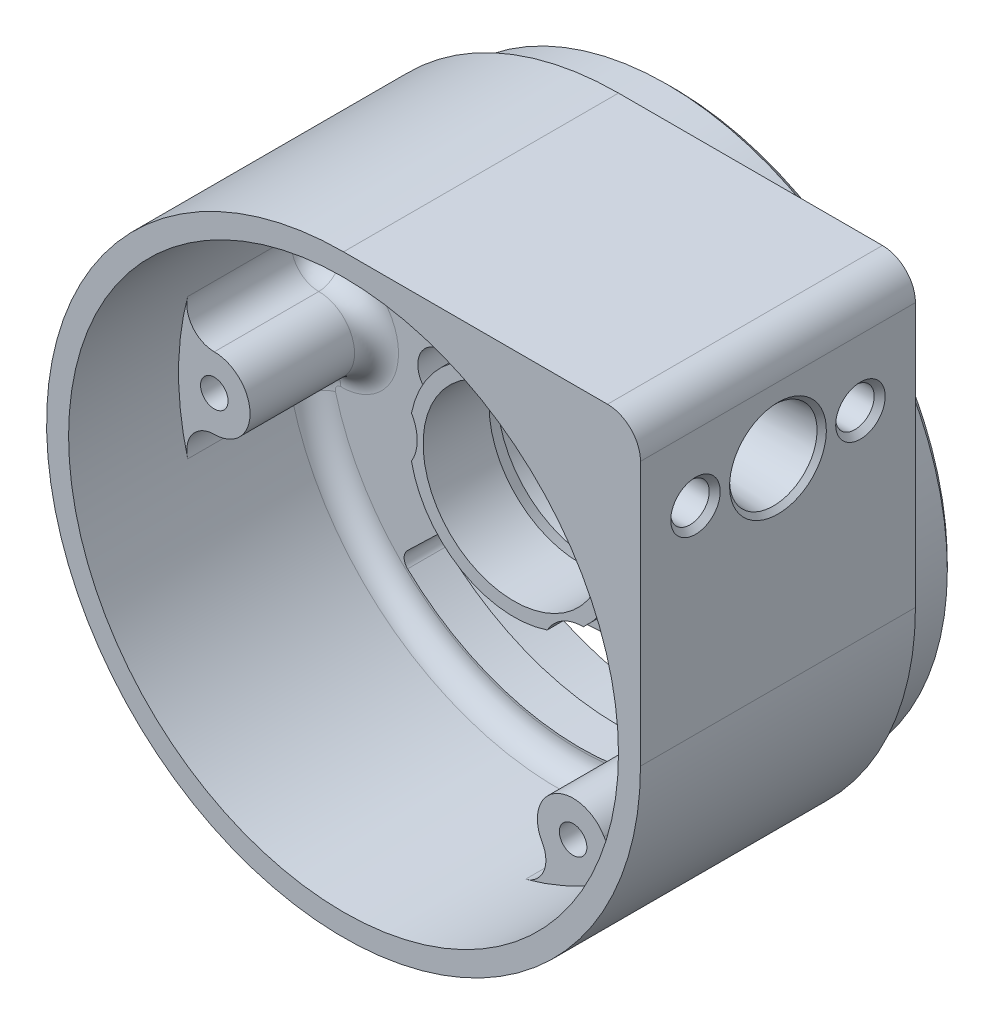
SolidWorks part; units mm, degrees
ref_plane "Front Plane" through (0, 0, 0) normal (0, 0, 1) x (1, 0, 0)
ref_plane "Top Plane" through (0, 0, 0) normal (0, 1, 0) x (1, 0, 0)
ref_plane "Right Plane" through (0, 0, 0) normal (1, 0, 0) x (0, 0, -1)
sketch "Sketch1" plane through (0, 0, 0) normal (0, 0, 1) x (1, 0, 0)
  line L0 (-12.5, 0) -> (0, 0) construction
  line L1 (0, 0) -> (6.25, 10.8253) construction
  line L2 (6.25, -10.8253) -> (0, 0) construction
  circle A0 centre (0, 0) radius 27
  circle A1 centre (0, 0) radius 12.5 construction
  circle A2 centre (0, 0) radius 7.75
  circle A3 centre (0, 0) radius 3 construction
  circle A4 centre (6.25, 10.8253) radius 2.25
  circle A5 centre (-12.5, 0) radius 2.25
  circle A6 centre (6.25, -10.8253) radius 2.25
  dimension "D1" = 54
  dimension "D2" = 6
  dimension "D3" = 15.5
  dimension "D4" = 25
  dimension "D7" = 4.5
  dimension "D5" = 120
  dimension "D6" = 120
extrude "Boss-Extrude1" add sketch "Sketch1" along normal blind 21
sketch "Sketch2" plane through (0, 0, 21) normal (0, 0, 1) x (1, 0, 0)
  circle A0 centre (6.25, 10.8253) radius 3.75
  circle A1 centre (6.25, -10.8253) radius 3.75
  circle A2 centre (-12.5, 0) radius 3.75
  dimension "D1" = 7.5
extrude "Cut-Extrude1" cut sketch "Sketch2" against normal offset from surface (16.5 mm away) 4.5 up to face at (27, 0, 0)
sketch "Sketch3" plane through (0, 0, 21) normal (0, 0, 1) x (1, 0, 0)
  line L0 (13.9654, 0) -> (0, 13.9654) construction
  line L1 (0, -17.6777) -> (17.6777, 0) construction
  line L2 (0, -17.6777) -> (-17.6777, 0) construction
  line L3 (-17.6777, 0) -> (0, 17.6777) construction
  line L4 (17.6777, 0) -> (0, 17.6777) construction
  line L5 (0, -17.6777) -> (0, 17.6777) construction
  line L6 (-17.6777, 0) -> (17.6777, 0) construction
  line L7 (0, 13.9654) -> (-13.9654, 0) construction
  line L8 (-13.9654, 0) -> (0, -13.9654) construction
  line L9 (0, -13.9654) -> (13.9654, 0) construction
  line L10 (-17.9605, 0) -> (0, 17.9605)
  line L11 (17.9605, 0) -> (0, 17.9605)
  line L12 (0, -17.9605) -> (17.9605, 0)
  line L13 (0, -17.9605) -> (-17.9605, 0)
  circle A0 centre (13.9654, 0) radius 1.625 construction
  circle A1 centre (0, -13.9654) radius 1.625 construction
  circle A2 centre (-13.9654, 0) radius 1.625 construction
  circle A3 centre (0, 13.9654) radius 1.625 construction
  point P0 (0, 0)
  dimension "D2" = 3.25
  dimension "D3" = 1
  dimension "D1" = 25
  dimension "D4" = 0.2
sketch "Sketch5" plane through (0, 0, 21) normal (0, 0, 1) x (1, 0, 0)
  line L0 (0, 27) -> (24, 27)
  line L3 (27, 0) -> (27, 24)
  circle A0 centre (0, 0) radius 27 construction
  arc A1 (0, 27) -> (27, 0) centre (0, 0) cw
  arc A3 (24, 27) -> (27, 24) centre (24, 24) cw
  circle M11 centre (0, 0) radius 27
extrude "Boss-Extrude2" add sketch "Sketch5" against normal up to surface (21 mm away) contours A3 L0 M11 | M11 region at (20.9021, 20.9021, 21) up to face at (27, 0, 0)
sketch "Sketch8" plane through (0, 0, 0) normal (0, 0, -1) x (-1, 0, 0)
  circle A0 centre (0, 0) radius 8.625
  dimension "D1" = 17.25
extrude "Cut-Extrude5" cut sketch "Sketch8" against normal blind 2
chamfer "Chamfer2" distance 1 angle 72 1 edges at (-7.75, 0, 2) first distance on face at (-7.75, 0, 2)
sketch "Sketch9" plane through (0, 0, 21) normal (0, 0, 1) x (1, 0, 0)
  circle A0 centre (0, 0) radius 25
  dimension "D1" = 50
extrude "Cut-Extrude6" cut sketch "Sketch9" against normal offset from surface (17.5 mm away) 3.5 up to face at (-8.625, 0, 0)
sketch "Sketch10" plane through (0, 0, 3.5) normal (0, 0, 1) x (1, 0, 0)
  line L0 (0, 0) -> (11.1505, 11.1233) construction
  line L1 (0, 0) -> (4.0578, -15.2183) construction
  line L2 (0, 0) -> (-15.2083, 4.095) construction
  line L3 (0, 0) -> (-2.716, 15.5141) construction
  line L4 (0, 0) -> (-12.0776, -10.1091) construction
  line L5 (0, 0) -> (13.8224, -5.0501) construction
  line L6 (-14.21, 3.8262) -> (-12.2736, 3.3048)
  line L7 (-2.1919, 12.5203) -> (-2.5377, 14.4956)
  line L8 (10.4185, 10.3931) -> (8.9988, 8.9768)
  line L9 (11.9388, -4.3619) -> (14.7936, -5.4049)
  line L10 (3.7914, -14.2193) -> (3.2748, -12.2816)
  line L11 (-9.747, -8.1584) -> (-11.2847, -9.4455)
  circle A0 centre (0, 0) radius 15.75 construction
  circle A1 centre (0, 0) radius 11.75 construction
  circle A2 centre (6.25, 10.8253) radius 2.25 construction
  arc A3 (-1.6579, 15.6625) -> (10.3708, 11.8537) centre (0, 0) cw
  arc A4 (14.3931, -6.3954) -> (5.0802, -14.9082) centre (0, 0) cw
  arc A5 (-15.451, 3.0545) -> (-12.7351, -9.2671) centre (0, 0) ccw
  arc A6 (-11.0713, 3.9355) -> (-2.9277, 11.3794) centre (0, 0) cw
  arc A7 (8.9439, 7.6203) -> (11.3187, -3.1542) centre (0, 0) cw
  arc A8 (2.1275, -11.5558) -> (-8.391, -8.2252) centre (0, 0) cw
  arc A9 (-8.391, -8.2252) -> (-9.747, -8.1584) centre (-9.1051, -8.9252) ccw
  arc A10 (2.1275, -11.5558) -> (3.2748, -12.2816) centre (2.3085, -12.5393) cw
  arc A11 (3.7914, -14.2193) -> (5.0802, -14.9082) centre (4.7577, -13.9616) ccw
  arc A12 (11.3187, -3.1542) -> (11.9388, -4.3619) centre (12.282, -3.4227) ccw
  arc A13 (14.3931, -6.3954) -> (13.8224, -5.0501) centre (13.4792, -5.9894) ccw
  arc A14 (8.9439, 7.6203) -> (8.9988, 8.9768) centre (9.7051, 8.2689) cw
  arc A15 (10.4185, 10.3931) -> (10.3708, 11.8537) centre (9.7123, 11.1011) ccw
  arc A16 (-2.5377, 14.4956) -> (-1.6579, 15.6625) centre (-1.5527, 14.6681) cw
  arc A17 (-2.9277, 11.3794) -> (-2.1919, 12.5203) centre (-3.1769, 12.3479) ccw
  arc A18 (-11.0713, 3.9355) -> (-12.2736, 3.3048) centre (-12.0136, 4.2704) cw
  arc A19 (-14.21, 3.8262) -> (-15.451, 3.0545) centre (-14.47, 2.8606) ccw
  arc A20 (-12.7351, -9.2671) -> (-11.2847, -9.4455) centre (-11.9266, -8.6787) ccw
  point P23 (-9.0103, -7.5417)
  point P26 (3.0272, -11.3533)
  point P31 (11.0365, -4.0322)
  point P37 (8.3187, 8.2983)
  point P46 (-2.0262, 11.574)
  point P49 (-11.3459, 3.055)
  dimension "D1" = 23.5
  dimension "D2" = 31.5
  dimension "D6" = 55
  dimension "D9" = 1
  dimension "D3" = 120
  dimension "D4" = 120
  dimension "D5" = 1
  dimension "D7" = 55
  dimension "D8" = 55
sketch "Sketch11" plane through (0, 0, 3.5) normal (0, 0, 1) x (1, 0, 0)
  line L0 (-3.3134, 13.3589) -> (-5.2425, 21.1366)
  line L1 (-13.0084, 4.4969) -> (-20.5819, 7.1151)
  line L2 (10.3986, 9.0171) -> (16.4528, 14.2669)
  line L3 (-14.21, 3.8262) -> (-12.2736, 3.3048) construction
  line L4 (-2.1919, 12.5203) -> (-2.5377, 14.4956) construction
  line L5 (13.2259, -3.81) -> (20.9261, -6.0282)
  line L6 (2.6097, -13.514) -> (4.1291, -21.382)
  line L7 (-9.9125, -9.549) -> (-15.6836, -15.1084)
  line L8 (0, 0) -> (-3.9736, 12.1676) construction
  line L9 (0, 0) -> (12.5242, -2.6426) construction
  arc A0 (-3.9736, 12.1676) -> (-11.7627, 5.0477) centre (0, 0) ccw
  circle A1 centre (0, 0) radius 25 construction
  arc A2 (-21.1843, 8.4299) -> (-20.5819, 7.1151) centre (-20.2552, 8.0602) ccw
  arc A3 (-6.4981, 21.8544) -> (-21.1843, 8.4299) centre (0, 0) ccw
  arc A4 (-11.7627, 5.0477) -> (-13.0084, 4.4969) centre (-12.6816, 5.4421) cw
  arc A5 (-3.9736, 12.1676) -> (-3.3134, 13.3589) centre (-4.284, 13.1182) ccw
  arc A6 (-5.2425, 21.1366) -> (-6.4981, 21.8544) centre (-6.2131, 20.8959) ccw
  arc A7 (10.2528, 7.6629) -> (10.3986, 9.0171) centre (11.0538, 8.2616) cw
  arc A8 (17.8927, 14.1312) -> (16.4528, 14.2669) centre (17.1079, 13.5114) ccw
  arc A9 (22.1755, -5.2997) -> (17.8927, 14.1312) centre (0, 0) ccw
  arc A10 (20.9261, -6.0282) -> (22.1755, -5.2997) centre (21.2029, -5.0672) ccw
  arc A11 (12.5242, -2.6426) -> (13.2259, -3.81) centre (13.5027, -2.849) ccw
  arc A12 (12.5242, -2.6426) -> (10.2528, 7.6629) centre (0, 0) ccw
  arc A13 (1.5099, -12.7106) -> (2.6097, -13.514) centre (1.6279, -13.7037) cw
  arc A14 (3.2916, -22.5611) -> (4.1291, -21.382) centre (3.1473, -21.5716) ccw
  arc A15 (-15.6774, -16.5547) -> (3.2916, -22.5611) centre (0, 0) ccw
  arc A16 (-15.6836, -15.1084) -> (-15.6774, -16.5547) centre (-14.9898, -15.8286) ccw
  arc A17 (-8.5507, -9.525) -> (-9.9125, -9.549) centre (-9.2187, -10.2692) ccw
  arc A18 (-8.5507, -9.525) -> (1.5099, -12.7106) centre (0, 0) ccw
  dimension "D3" = 10
  dimension "D4" = 2.2
  dimension "D5" = 1
  dimension "D1" = 4
  dimension "D2" = 4
  dimension "D6" = 120
extrude "Cut-Extrude7" cut sketch "Sketch11" against normal through all
sketch "Sketch13" plane through (0, 0, 0) normal (0, 0, -1) x (-1, 0, 0)
  circle A0 centre (0, 0) radius 24.2
  arc A1 (-27, 0) -> (0, 27) centre (0, 0) ccw construction
  circle A2 centre (0, 0) radius 25.5
  dimension "D1" = 2.8
  dimension "D2" = 1.5
extrude "Boss-Extrude3" add sketch "Sketch13" along normal blind 5
fillet "Fillet2" radius 1 1 edges at (-24.2, 0, 0)
chamfer "Chamfer3" distance 0.6 angle 45 1 edges at (-25.5, 0, -5)
sketch "Sketch14" plane through (0, 0, 3.5) normal (0, 0, 1) x (1, 0, 0)
  line L0 (0, 0) -> (-25, 0) construction
  line L1 (0, 0) -> (12.5, 21.6506) construction
  line L2 (0, 0) -> (12.5, -21.6506) construction
  circle A0 centre (0, 0) radius 25 construction
  circle A1 centre (0, 0) radius 25 construction
  circle A2 centre (6.25, -10.8253) radius 2.25 construction
  circle A3 centre (6.25, -10.8253) radius 2.25 construction
  circle A4 centre (6.25, 10.8253) radius 2.25 construction
  circle A5 centre (-12.5, 0) radius 2.25 construction
  circle A6 centre (6.25, 10.8253) radius 2.25 construction
  circle A7 centre (-12.5, 0) radius 2.25 construction
  circle A8 centre (-21.75, 0) radius 3.25 construction
  arc A9 (-21.75, 3.25) -> (-24.169, 6.392) centre (-21.75, 5.7522) cw
  arc A10 (-21.75, -3.25) -> (-24.169, -6.392) centre (-21.75, -5.7522) ccw
  arc A11 (-21.75, 3.25) -> (-21.75, -3.25) centre (-21.75, 0) cw
  arc A12 (-24.169, 6.392) -> (-24.169, -6.392) centre (0, 0) ccw
  arc A13 (13.6896, 17.2111) -> (17.6201, 17.735) centre (15.8566, 15.9599) cw
  arc A14 (8.0604, 20.4611) -> (6.5489, 24.127) centre (5.8934, 21.7122) ccw
  arc A15 (13.6896, 17.2111) -> (8.0604, 20.4611) centre (10.875, 18.8361) cw
  arc A16 (17.6201, 17.735) -> (6.5489, 24.127) centre (0, 0) ccw
  circle A17 centre (10.875, 18.8361) radius 3.25 construction
  arc A18 (8.0604, -20.4611) -> (6.5489, -24.127) centre (5.8934, -21.7122) cw
  arc A19 (13.6896, -17.2111) -> (17.6201, -17.735) centre (15.8566, -15.9599) ccw
  arc A20 (8.0604, -20.4611) -> (13.6896, -17.2111) centre (10.875, -18.8361) cw
  arc A21 (6.5489, -24.127) -> (17.6201, -17.735) centre (0, 0) ccw
  circle A22 centre (10.875, -18.8361) radius 3.25 construction
  circle A23 centre (-21.75, 0) radius 1.25
  circle A24 centre (10.875, -18.8361) radius 1.25
  circle A25 centre (10.875, 18.8361) radius 1.25
  point P49 (0, 0)
  dimension "D1" = 6.5
  dimension "D3" = 2.5
  dimension "D2" = 3
extrude "Boss-Extrude4" add sketch "Sketch14" along normal offset from surface (11.5 mm away) 6 up to face at (25, 0, 21)
fillet "Fillet4" radius 2 12 edges at (8.2067, 22.666, 3.5) (-12.5, 21.6506, 3.5) (-23.7327, 4.2257, 3.5) (-18.5, 0, 3.5) (-23.7327, -4.2257, 3.5) (-12.5, -21.6506, 3.5) (8.2067, -22.666, 3.5) (9.25, -16.0215, 3.5) (15.5259, -18.4402, 3.5) (25, 0, 3.5) (15.5259, 18.4402, 3.5) (9.25, 16.0215, 3.5)
sketch "Sketch16" plane through (0, 0, 21) normal (0, 0, 1) x (1, 0, 0)
  line L2 (27, 0) -> (27, 24)
  line L3 (24, 27) -> (0, 27)
  line L4 (27, 0) -> (27, 24)
  line L5 (24, 27) -> (0, 27)
  circle A0 centre (0, 0) radius 25 construction
  circle A1 centre (0, 0) radius 25
  arc A2 (0, 27) -> (27, 0) centre (0, 0) ccw
  arc A3 (27, 24) -> (24, 27) centre (24, 24) ccw
  arc A4 (0, 27) -> (27, 0) centre (0, 0) ccw
  arc A5 (27, 24) -> (24, 27) centre (24, 24) ccw
  dimension "D1" = 0
extrude "Boss-Extrude5" add sketch "Sketch16" along normal blind 4
sketch "Sketch6" plane through (27, 0, 0) normal (1, 0, 0) x (0, 0, -1)
  line L0 (-12.5, 27) -> (-12.5, -27) construction
  line L3 (0, 27) -> (-25, 27) construction
  line L5 (-25, -27) -> (0, -27) construction
  circle A0 centre (-12.5, 18) radius 4
  dimension "D1" = 8
  dimension "D2" = 9
extrude "Cut-Extrude4" cut sketch "Sketch6" against normal blind 6 draft 3
fillet "Fillet3" radius 1 1 edges at (25.5, 0, 0)
sketch "Sketch17" plane through (27, 0, 0) normal (1, 0, 0) x (0, 0, -1)
  line L0 (-25, 18) -> (0, 18) construction
  line L1 (-25, 0) -> (-25, 24) construction
  line L2 (0, 24) -> (0, 0) construction
  line L3 (-20, 18) -> (-5, 18) construction
  circle A2 centre (-12.5, 18) radius 4 construction
  circle A3 centre (-12.5, 18) radius 4 construction
  circle A4 centre (-20, 18) radius 1.75
  circle A5 centre (-5, 18) radius 1.75
  point P13 (-12.5, 18)
  dimension "D1" = 3.5
  dimension "D2" = 15
extrude "Cut-Extrude8" cut sketch "Sketch17" against normal blind 5
chamfer "Chamfer4" distance 1 angle 45 2 edges at (22, 19.75, 5) (22, 19.75, 20)
chamfer "Chamfer5" distance 0.5 angle 45 2 edges at (27, 19.75, 20) (27, 19.75, 5)
chamfer "Chamfer6" distance 0.4 angle 45 1 edges at (27, 22, 12.5) first distance on face at (27, 20.25, 20)
sketch "Sketch18" plane through (0, 0, 3.5) normal (0, 0, 1) x (1, 0, 0)
  circle A0 centre (0, 0) radius 8.2626 construction
  circle A1 centre (0, 0) radius 8.2626
  circle A2 centre (0, 0) radius 9.5126 construction
  circle A3 centre (-12.5, 0) radius 3.7 construction
  circle A4 centre (6.25, -10.8253) radius 3.7 construction
  circle A5 centre (6.25, 10.8253) radius 3.7 construction
  arc A6 (-9.322, -1.8948) -> (3.02, -9.0205) centre (0, 0) ccw
  arc A7 (-9.322, -1.8948) -> (-9.322, 1.8948) centre (-12.5, 0) ccw
  arc A8 (-9.322, 1.8948) -> (3.02, 9.0205) centre (0, 0) cw
  arc A9 (3.02, 9.0205) -> (6.302, 7.1257) centre (6.25, 10.8253) ccw
  arc A10 (6.302, 7.1257) -> (6.302, -7.1257) centre (0, 0) cw
  arc A11 (6.302, -7.1257) -> (3.02, -9.0205) centre (6.25, -10.8253) ccw
  point P20 (3.0278, -9.0068)
  dimension "D1" = 1.25
  dimension "D2" = 7.4
extrude "Boss-Extrude6" add sketch "Sketch18" along normal blind 6
fillet "Fillet5" radius 1.5 3 edges at (9.5126, 0, 3.5) (-4.7563, 8.2382, 3.5) (-4.7563, -8.2382, 3.5)
sketch "Sketch20" plane through (0, 0, 3.5) normal (0, 0, 1) x (1, 0, 0)
  circle A0 centre (0, 0) radius 25 construction
  circle A1 centre (0, 0) radius 25
extrude "Boss-Extrude7" [suppressed] add sketch "Sketch20" against normal blind 0.2
sketch "Sketch19" plane through (0, 0, 15) normal (0, 0, 1) x (1, 0, 0)
  circle A0 centre (-21.75, 0) radius 1.25 construction
  circle A1 centre (10.875, -18.8361) radius 1.25 construction
  circle A2 centre (10.875, 18.8361) radius 1.25 construction
  circle A3 centre (-21.75, 0) radius 1.25
  circle A4 centre (10.875, -18.8361) radius 1.25
  circle A5 centre (10.875, 18.8361) radius 1.25
extrude "Cut-Extrude9" cut sketch "Sketch19" against normal through all
